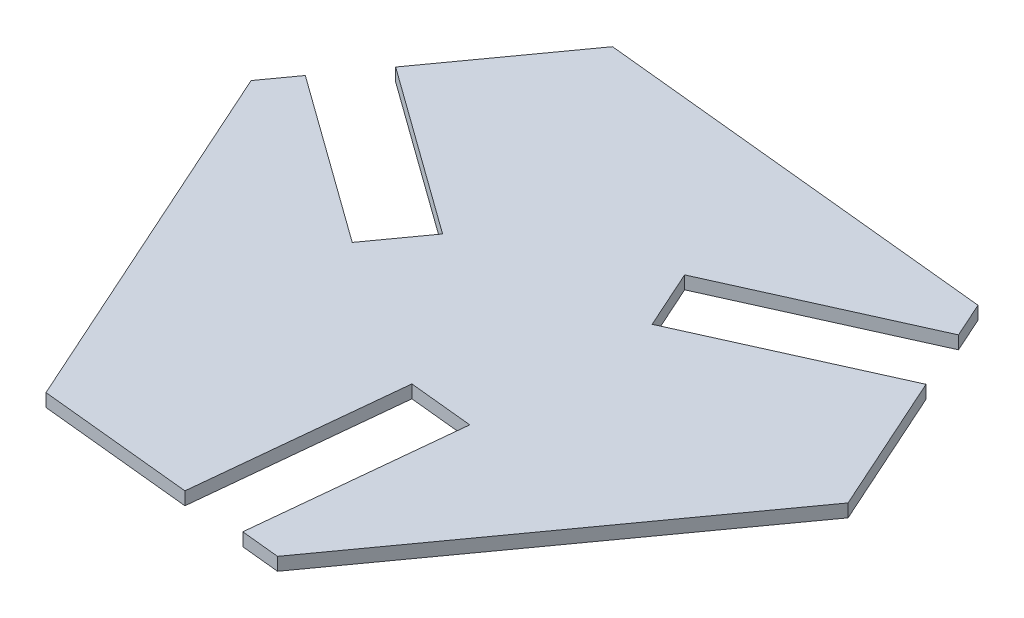
SolidWorks part; units mm, degrees
ref_plane "Front Plane" through (0, 0, 0) normal (0, 0, 1) x (1, 0, 0)
ref_plane "Top Plane" through (0, 0, 0) normal (0, 1, 0) x (1, 0, 0)
ref_plane "Right Plane" through (0, 0, 0) normal (1, 0, 0) x (0, 0, -1)
sketch "Sketch1" plane through (0, 0, 0) normal (0, 1, 0) x (1, 0, 0)
  line L0 (-43.2537, 70.3109) -> (-80.3816, 18.7962) construction
  line L1 (-43.2537, 70.3109) -> (56.4688, 60.2144)
  line L2 (82.5179, 2.3033) -> (23.9128, -79.0106)
  line L3 (-39.2642, -72.6142) -> (-80.3816, 18.7962)
  line L4 (60.3762, 51.5278) -> (56.4688, 60.2144)
  line L5 (82.5179, 2.3033) -> (56.4688, 60.2144) construction
  line L6 (-74.8124, 26.5234) -> (-33.6007, -3.179)
  line L7 (-33.6007, -3.179) -> (-24.3187, 9.6997)
  line L8 (-24.3187, 9.6997) -> (-65.5304, 39.4021)
  line L9 (-65.5304, 39.4021) -> (-43.2537, 70.3109)
  line L10 (-74.8124, 26.5234) -> (-80.3816, 18.7962)
  line L11 (66.8884, 37.05) -> (82.5179, 2.3033)
  line L12 (20.5595, 16.2107) -> (66.8884, 37.05)
  line L13 (60.3762, 51.5278) -> (14.0473, 30.6885)
  line L14 (14.0473, 30.6885) -> (20.5595, 16.2107)
  line L15 (14.4363, -78.0512) -> (23.9128, -79.0106)
  line L16 (-39.2642, -72.6142) -> (23.9128, -79.0106) construction
  line L17 (-1.358, -76.4521) -> (-39.2642, -72.6142)
  line L18 (3.7591, -25.9104) -> (-1.358, -76.4521)
  line L19 (14.4363, -78.0512) -> (19.5534, -27.5096)
  line L20 (19.5534, -27.5096) -> (3.7591, -25.9104)
  circle A1 centre (0, 0) radius 76.2 construction
  point P4 (69.4933, 31.2589)
  point P5 (-7.6757, -75.8124)
  point P8 (-61.8176, 44.5536)
  dimension "D2" = 15.875
  dimension "D6" = 152.4
  dimension "D1" = 63.5
  dimension "D3" = 50.8
  dimension "D4" = 38.1
  dimension "D5" = 3
extrude "Boss-Extrude2" add sketch "Sketch1" along normal blind 3.175
